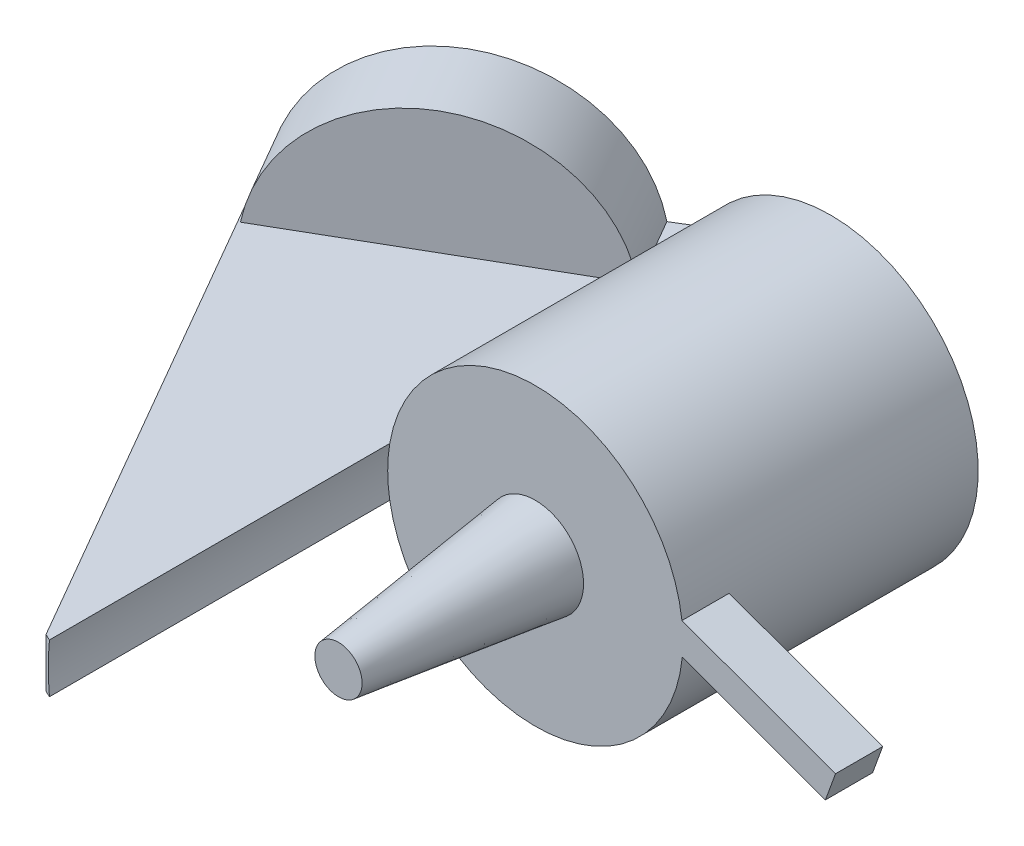
SolidWorks part; units mm, degrees
ref_plane "Front Plane" through (0, 0, 0) normal (0, 0, 1) x (1, 0, 0)
ref_plane "Top Plane" through (0, 0, 0) normal (0, 1, 0) x (1, 0, 0)
ref_plane "Right Plane" through (0, 0, 0) normal (1, 0, 0) x (0, 0, -1)
sketch "Sketch1" plane through (0, 0, 0) normal (0, 0, 1) x (1, 0, 0)
  line L0 (0, 0) -> (1.2826, 3.5238) construction
  line L5 (1.2826, 3.5238) -> (46.6088, -12.9735) construction
  line L6 (1.2826, 3.5238) -> (18.6539, -2.7988) construction
  line L7 (1.2826, 3.5238) -> (6.2305, 17.1183) construction
  line L8 (0, 0) -> (-31.7364, 0) construction
  line L9 (10.6795, 0.1036) -> (29.4734, -6.7368)
  line L10 (10.6795, 0.1036) -> (11.7056, 2.9227)
  line L11 (11.7056, 2.9227) -> (30.4994, -3.9177)
  line L12 (29.4734, -6.7368) -> (30.4994, -3.9177)
  line L13 (-3, 2.5) -> (-3, -2.5)
  line L14 (-50, 2.5) -> (0, 2.5)
  line L15 (-50, 2.5) -> (-50, -2.5)
  line L16 (-50, -2.5) -> (0, -2.5)
  line L17 (0, 2.5) -> (0, -2.5)
  circle A0 centre (0, 0) radius 4.9
  circle A1 centre (0, 0) radius 15
  circle A2 centre (0, 0) radius 2.4
  point P17 (-50, 0)
  point P18 (0, 0)
  dimension "D1" = 4.8
  dimension "D2" = 9.8
  dimension "D3" = 30
  dimension "D4" = 5
  dimension "D5" = 3.75
  dimension "D6" = 90
  dimension "D7" = 20
  dimension "D8" = 10
  dimension "D9" = 3
  dimension "D10" = 50
  dimension "D11" = 110
  dimension "D12" = 3
extrude "Boss-Extrude1" add sketch "Sketch1" against normal blind 15 and the other way blind 15 contours A1
extrude "Boss-Extrude2" add sketch "Sketch1<3>" against normal blind 4.8 from surface contours A2 starting at face at (15, 0, -15)
sketch "Sketch1<3>" plane through (0, 0, 0) normal (0, 0, 1) x (1, 0, 0) same geometry as "Sketch1"
ref_plane "Plane1" through (0, 0, 35) normal (0, 0, 1) x (1, 0, 0)
ref_plane "Plane2" through (0, 0, 15) normal (0, 0, 1) x (1, 0, 0)
sketch "Sketch4" plane through (0, 0, 15) normal (0, 0, 1) x (1, 0, 0)
  circle A0 centre (0, 0) radius 4.9
  circle A1 centre (0, 0) radius 4.9 construction
sketch "Sketch3" plane through (0, 0, 35) normal (0, 0, 1) x (1, 0, 0)
  circle A0 centre (0, 0) radius 2.4
  dimension "D1" = 4.8
loft "Loft2" add section "Sketch4" section "Sketch3" connector at (0.2431, 4.894, 15) connector at (0.2903, 2.3824, 35)
extrude "Boss-Extrude3" add sketch "Sketch1<5>" against normal blind 4.8 from surface contours L11 L12 L9 L10 starting at face at (15, 0, 15)
sketch "Sketch1<5>" plane through (0, 0, 0) normal (0, 0, 1) x (1, 0, 0) same geometry as "Sketch1"
extrude "Boss-Extrude4" add sketch "Sketch1<7>" along normal blind 60 contours A1 L14 L15 L16 region at (-32.4651, 0, 0)
sketch "Sketch1<7>" plane through (0, 0, 0) normal (0, 0, 1) x (1, 0, 0) same geometry as "Sketch1"
extrude "Boss-Extrude5" add sketch "Sketch1<8>" against normal blind 38 contours A1 L14 L15 L16 | L14 A1 L16 A0 | A2 L13 L14 A0 L16 region at (-9.8024, 0, 0) region at (-32.4651, 0, 0) region at (-3.8513, 0, 0)
sketch "Sketch1<8>" plane through (0, 0, 0) normal (0, 0, 1) x (1, 0, 0) same geometry as "Sketch1"
sketch "Sketch6" plane through (0, 0, 0) normal (0, 1, 0) x (1, 0, 0)
  line L0 (0, 31.0233) -> (0, -56.4767) construction
  line L1 (0, -56.4767) -> (-93.8788, -12.7002) construction
  line L2 (8.2583, -60.3276) -> (-33.0417, 11.2061) construction
  line L3 (-20.0513, 18.7061) -> (0, 31.0233) construction
  line L4 (0, -56.4767) -> (18.1191, -64.9257) construction
  line L5 (-15.4432, -49.2754) -> (39.4972, 68.5446)
  line L6 (-15.4432, -49.2754) -> (-46.0321, 3.7061) construction
  line L7 (-20.0513, 18.7061) -> (-46.0321, 3.7061) construction
  line L8 (39.4972, 68.5446) -> (29.5278, 73.1934)
  line L9 (29.5278, 73.1934) -> (0, 31.0233)
  point P4 (-15.4432, -49.2754)
  point P11 (0, 0)
  point P14 (-33.0417, 11.2061)
  point P15 (-36.2209, 12.6886)
  point P16 (0, 0)
  point P18 (-79.0612, 32.6654)
  point P19 (0, -56.4767)
  point P20 (18.1191, -64.9257)
  point P21 (-33.0417, 11.2061)
  point P22 (-46.0321, 3.7061)
  point P23 (0, 0)
  dimension "D1" = 65
  dimension "D2" = 35
  dimension "D3" = 25
  dimension "D4" = 82.6
  dimension "D5" = 30
  dimension "D6" = 87.5
  dimension "D7" = 130
  dimension "D8" = 11
  dimension "D9" = 100
sketch "Sketch7" plane through (0, 0, 0) normal (0, 1, 0) x (1, 0, 0)
  line L0 (-15.4432, -49.2754) -> (0, -56.4767)
  line L1 (0, -56.4767) -> (-93.8788, -12.7002) construction
  line L2 (-15.4432, -49.2754) -> (-46.0321, 3.7061) construction
  line L3 (-15.4432, -49.2754) -> (-46.0321, 3.7061)
  line L4 (-46.0321, 3.7061) -> (-20.0513, 18.7061)
  line L7 (0, 56.4517) -> (-64.9778, 56.4517)
  line L8 (-64.9778, 56.4517) -> (-64.9778, -114.6241)
  line L9 (-64.9778, -114.6241) -> (0, -114.6241)
  line L10 (0, -114.6241) -> (0, -56.4767)
  line L11 (0, 59.3803) -> (0, 15) construction
  line L12 (0, 15) -> (-17.9116, 15) construction
  line L13 (-14.7902, 15) -> (-3, 15) construction
  line L14 (0, 56.4517) -> (0, 15)
  line L16 (-20.0513, 18.7061) -> (0, 31.0233)
  line L17 (-20.0513, 18.7061) -> (0, 31.0233) construction
  line L19 (-8.25, 15) -> (-8.25, 25.9555)
  line L20 (-8.25, 15) -> (0, 15)
  line L23 (0, 31.0233) -> (0, -56.4767) construction
  point P13 (0, 0)
  point P21 (0, 0)
  point P27 (-8.25, 11.1674)
  point P31 (0, 59.3803)
  point P32 (0, 0)
  dimension "D1" = 8.25
extrude "Cut-Extrude1" cut sketch "Sketch7" against normal through all both and the other way through all contours L4 L16 L14 L7 L8 L9 L10 L0 L3 | L19 L20 L14 L16 region at (-36.8024, 0, 33.858) region at (-3.8667, 0, -21.824)
ref_plane "Plane3" through (-33.0417, 0, -11.2061) normal (-0.5, 0, -0.866) x (-0.866, 0, 0.5)
ref_plane "Plane4" through (0, 0, 0) normal (0, -1, 0) x (-0.866, 0, 0.5)
sketch "Sketch8" plane through (-33.0417, 0, -11.2061) normal (-0.5, 0, -0.866) x (-0.866, 0, 0.5)
  circle A0 centre (0, 0) radius 15
  dimension "D1" = 30
extrude "Boss-Extrude6" add sketch "Sketch8" against normal blind 8
ref_plane "Plane5" through (-17.5976, 7.3959, 10.16) normal (-0.8138, 0.342, 0.4698) x (-0.5, 0, -0.866)
sketch "Sketch10" plane through (-33.0417, 0, -11.2061) normal (-0.5, 0, -0.866) x (-0.866, 0, 0.5)
  line L0 (0, 47.2358) -> (0, -47.2358) construction
  line L2 (-42.5612, 0) -> (42.5612, 0) construction
  line L4 (5.2265, 0) -> (64.6397, 0) construction
  line L5 (0, 0) -> (32.388, 38.5985) construction
  point P5 (0, 0)
  point P10 (0, 0)
  dimension "D1" = 140
